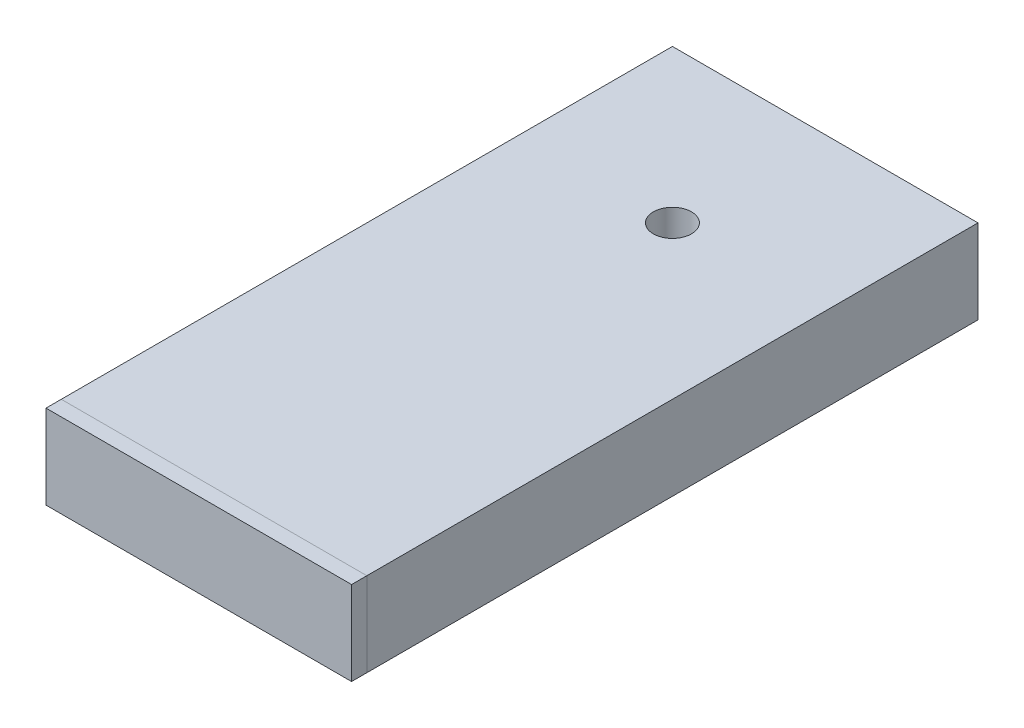
SolidWorks part; units mm, degrees
material "Maple"
ref_plane "Front Plane" through (0, 0, 0) normal (0, 0, 1) x (1, 0, 0)
ref_plane "Top Plane" through (0, 0, 0) normal (0, 1, 0) x (1, 0, 0)
ref_plane "Right Plane" through (0, 0, 0) normal (1, 0, 0) x (0, 0, -1)
sketch "Sketch1" plane through (0, 0, 0) normal (0, 1, 0) x (1, 0, 0)
  line L1 (-31.75, 63.5) -> (31.75, 63.5)
  line L2 (-31.75, 63.5) -> (-31.75, -63.5)
  line L3 (-31.75, -63.5) -> (31.75, -63.5)
  line L4 (31.75, 63.5) -> (31.75, -63.5)
  line L5 (-31.75, 63.5) -> (31.75, -63.5) construction
  line L6 (-31.75, -63.5) -> (31.75, 63.5) construction
  point P0 (0, 0)
  dimension "D1" = 63.5
  dimension "D2" = 127
extrude "Boss-Extrude1" add sketch "Sketch1" along normal blind 19.05
sketch "Sketch2" plane through (0, 19.05, 0) normal (0, 1, 0) x (1, 0, 0)
  line L0 (-31.75, -63.5) -> (31.75, -63.5) construction
  circle A0 centre (0, 31.75) radius 3.9688
  dimension "D1" = 7.9375
  dimension "D2" = 95.25
extrude "Cut-Extrude1" cut sketch "Sketch2" against normal through all
sketch "Sketch3" plane through (0, 0, 63.5) normal (0, 0, 1) x (1, 0, 0)
  line L1 (-31.75, 19.05) -> (31.75, 19.05)
  line L2 (-31.75, 19.05) -> (-31.75, 0)
  line L3 (-31.75, 0) -> (31.75, 0)
  line L4 (31.75, 19.05) -> (31.75, 0)
  line L5 (-31.75, 19.05) -> (31.75, 0) construction
  line L6 (-31.75, 0) -> (31.75, 19.05) construction
  point P0 (0, 9.525)
extrude "Boss-Extrude2" add sketch "Sketch3" along normal blind 3.175 separate body
sketch "Sketch4" plane through (0, 0, -63.5) normal (0, 0, -1) x (-1, 0, 0)
  line L0 (-4.3656, 0) -> (4.3656, 0) construction
  line L1 (-31.75, 0) -> (-4.3656, 0)
  line L2 (-31.75, 0) -> (-31.75, 1.5875)
  line L3 (-31.75, 1.5875) -> (-4.3656, 1.5875)
  line L4 (-4.3656, 0) -> (-4.3656, 1.5875)
  line L5 (4.3656, 1.5875) -> (31.75, 1.5875)
  line L6 (4.3656, 1.5875) -> (4.3656, 0)
  line L7 (4.3656, 0) -> (31.75, 0)
  line L8 (31.75, 1.5875) -> (31.75, 0)
  dimension "D1" = 1.5875
  dimension "D2" = 8.7312
extrude "Cut-Extrude2" cut sketch "Sketch4" against normal through all
sketch "Sketch5" plane through (0, 0, 66.675) normal (0, 0, 1) x (1, 0, 0)
  line L1 (-4.3656, 1.5875) -> (4.3656, 1.5875)
  line L2 (-4.3656, 1.5875) -> (-4.3656, 0)
  line L3 (-4.3656, 0) -> (4.3656, 0)
  line L4 (4.3656, 1.5875) -> (4.3656, 0)
extrude "Cut-Extrude3" cut sketch "Sketch5" against normal up to vertex (3.175 mm away) up to point (-4.3656, 0, 63.5)
